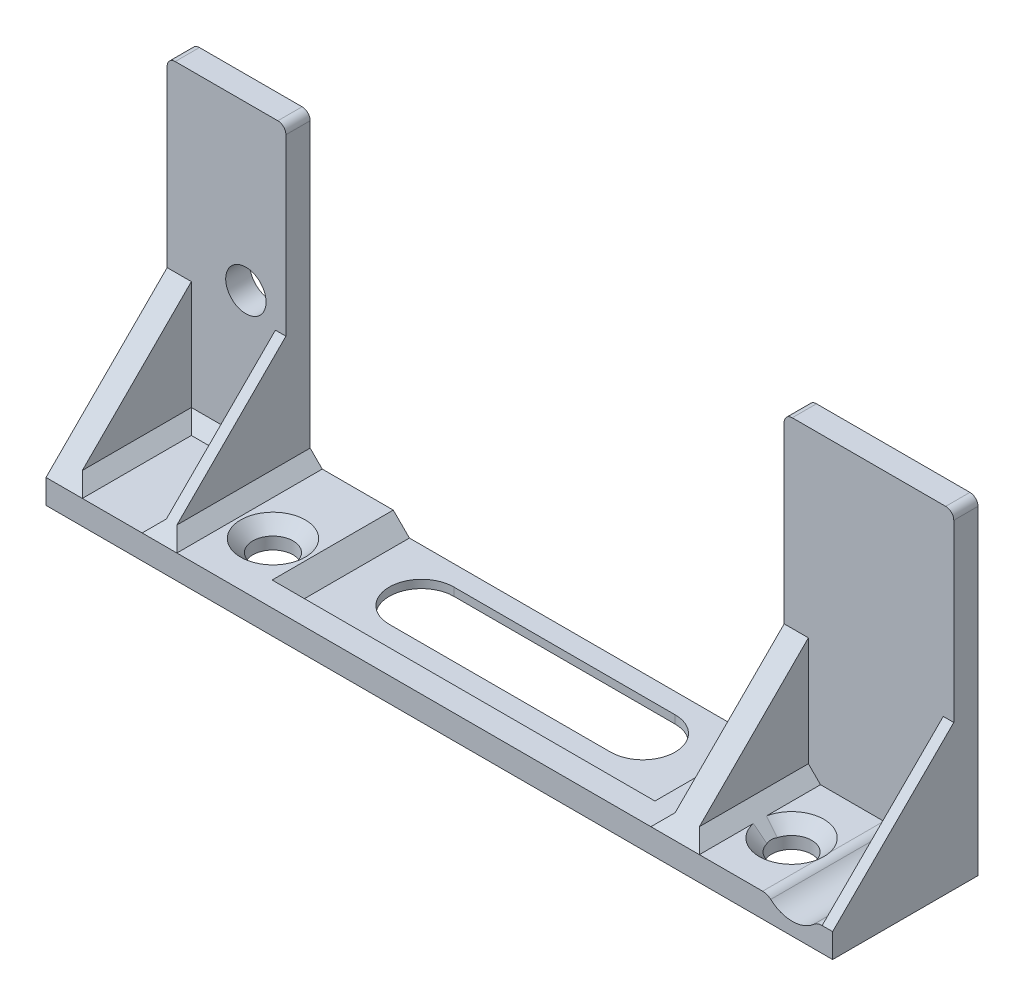
SolidWorks part; units mm, degrees
ref_plane "Plano frontal" through (0, 0, 0) normal (0, 0, 1) x (1, 0, 0)
ref_plane "Plano superior" through (0, 0, 0) normal (0, 1, 0) x (1, 0, 0)
ref_plane "Plano direito" through (0, 0, 0) normal (1, 0, 0) x (0, 0, -1)
sketch "Esboço1" plane through (0, 0, 0) normal (0, 0, 1) x (1, 0, 0)
  line L0 (62.4, 20.175) -> (-33, 20.175)
  line L1 (-34, 19.175) -> (-34, -20.425)
  line L2 (-34, -20.425) -> (63.4, -20.425)
  line L3 (63.4, -20.425) -> (63.4, 19.175)
  line L4 (17.9243, -6.9539) -> (16.3222, -6.7818)
  line L5 (17.9243, -6.9539) -> (18.9922, 2.9889)
  line L6 (18.9922, 2.9889) -> (17.3901, 3.161)
  line L7 (18.2952, -14.6385) -> (17.6127, -1.4836)
  line L8 (9.8273, -18.425) -> (14.7, -18.425)
  line L9 (7.4699, -16.019) -> (9.8273, -18.425)
  line L10 (1.1798, 17.6356) -> (-14.434, 18.7656)
  line L11 (-18.2939, 10.276) -> (-15.8632, 7.7952)
  line L12 (-18.2939, 15.175) -> (-18.2939, 10.276)
  line L13 (51.4, -14.825) -> (51.4, -6.825)
  line L14 (45.4, -14.825) -> (51.4, -14.825)
  line L15 (45.4, -6.825) -> (45.4, -14.825)
  line L16 (51.4, -6.825) -> (45.4, -6.825)
  line L17 (51.4, 7.175) -> (51.4, 15.175)
  line L18 (51.4, 15.175) -> (45.4, 15.175)
  line L19 (45.4, 15.175) -> (45.4, 7.175)
  line L20 (45.4, 7.175) -> (51.4, 7.175)
  line L21 (-29, -13.825) -> (-25, -13.825)
  line L22 (-25, -13.825) -> (-25, -7.825)
  line L23 (-29, -7.825) -> (-29, -13.825)
  line L24 (-25, -7.825) -> (-29, -7.825)
  line L25 (-25, 8.175) -> (-25, 14.175)
  line L26 (-25, 14.175) -> (-29, 14.175)
  line L27 (-29, 14.175) -> (-29, 8.175)
  line L28 (-29, 8.175) -> (-25, 8.175)
  line L29 (23.216, -4.505) -> (23.6432, -0.5279)
  line L30 (23.6432, -0.5279) -> (18.6718, 0.0061)
  line L31 (23.216, -4.505) -> (18.2446, -3.9711)
  arc A0 (-33, 20.175) -> (-34, 19.175) centre (-33, 19.175) ccw
  arc A1 (63.4, 19.175) -> (62.4, 20.175) centre (62.4, 19.175) ccw
  arc A2 (14.7, -18.425) -> (18.2952, -14.6385) centre (14.7, -14.825) ccw
  circle A3 centre (14.7, -14.825) radius 1.75
  circle A4 centre (0, 0) radius 17.675
  arc A5 (-14.434, 18.7656) -> (-18.2939, 15.175) centre (-14.6939, 15.175) ccw
  circle A6 centre (-14.6939, 15.175) radius 1.75
  circle A7 centre (0, 0) radius 1
  circle A8 centre (58.4, -14.825) radius 2
  circle A9 centre (-24.25, 0) radius 2.5
sketch "Esboço2" plane through (0, 0, 0) normal (0, 0, 1) x (1, 0, 0)
  line L8 (-19.2939, 20.175) -> (-19.2939, -17.425)
  line L9 (-18.2939, 15.175) -> (-18.2939, 10.276) construction
  line L10 (42.4, 20.175) -> (42.4, -17.425)
  line L11 (45.4, 15.175) -> (45.4, 7.175) construction
  line L20 (-19.2939, 20.175) -> (-33, 20.175)
  line L21 (42.4, -20.425) -> (63.4, -20.425)
  line L22 (9.8273, -18.425) -> (14.7, -18.425) construction
  line L23 (42.4, -20.425) -> (-19.2939, -20.425)
  line L33 (38.4, -19.425) -> (-9, -19.425)
  line L35 (-19.2939, -17.425) -> (-9, -17.425)
  line L40 (63.4, -20.425) -> (63.4, 19.175) construction
  line L41 (-34, -20.425) -> (63.4, -20.425) construction
  line L42 (-34, 19.175) -> (-34, -20.425) construction
  line L43 (62.4, 20.175) -> (-33, 20.175) construction
  line L44 (-9, -17.425) -> (-9, -19.425)
  line L45 (42.4, -17.425) -> (38.4, -17.425)
  line L46 (38.4, -17.425) -> (38.4, -19.425)
  line L52 (63.4, -20.425) -> (63.4, 19.175)
  line L53 (-34, -20.425) -> (-19.2939, -20.425)
  line L54 (-34, 19.175) -> (-34, -20.425)
  line L55 (62.4, 20.175) -> (42.4, 20.175)
  arc A0 (63.4, 19.175) -> (62.4, 20.175) centre (62.4, 19.175) ccw construction
  arc A1 (-33, 20.175) -> (-34, 19.175) centre (-33, 19.175) ccw construction
  arc A2 (63.4, 19.175) -> (62.4, 20.175) centre (62.4, 19.175) ccw
  arc A3 (-33, 20.175) -> (-34, 19.175) centre (-33, 19.175) ccw
  circle A4 centre (-24.25, 0) radius 2.5 construction
  circle A5 centre (-24.25, 0) radius 2.5
  circle A6 centre (58.4, -14.825) radius 2 construction
  circle A7 centre (58.4, -14.825) radius 2
  dimension "D1" = 1
  dimension "D2" = 3
  dimension "D3" = 1
  dimension "D4" = 25
  dimension "D5" = 25
  dimension "D6" = 3
  dimension "D7" = 3
extrude "Ressalto-extrusão1" add sketch "Esboço2" along normal blind 3
sketch "Esboço3" plane through (0, 0, 0) normal (0, 0, -1) x (-1, 0, 0)
  line L24 (-51.1, 14.875) -> (-51.1, 7.475)
  line L25 (-45.7, 14.875) -> (-51.1, 14.875)
  line L26 (-45.7, 7.475) -> (-45.7, 14.875)
  line L27 (-51.1, 7.475) -> (-45.7, 7.475)
  line L28 (-51.1, 14.875) -> (-51.1, 7.475)
  line L29 (-45.7, 14.875) -> (-51.1, 14.875)
  line L30 (-45.7, 7.475) -> (-45.7, 14.875)
  line L31 (-51.1, 7.475) -> (-45.7, 7.475)
  line L36 (-51.1, -7.125) -> (-51.1, -14.525)
  line L37 (-45.7, -7.125) -> (-51.1, -7.125)
  line L38 (-45.7, -14.525) -> (-45.7, -7.125)
  line L39 (-51.1, -14.525) -> (-45.7, -14.525)
  line L40 (-51.1, -7.125) -> (-51.1, -14.525)
  line L41 (-45.7, -7.125) -> (-51.1, -7.125)
  line L42 (-45.7, -14.525) -> (-45.7, -7.125)
  line L43 (-51.1, -14.525) -> (-45.7, -14.525)
  line L48 (25.3, 13.875) -> (25.3, 8.475)
  line L49 (28.7, 13.875) -> (25.3, 13.875)
  line L50 (28.7, 8.475) -> (28.7, 13.875)
  line L51 (25.3, 8.475) -> (28.7, 8.475)
  line L52 (25.3, 13.875) -> (25.3, 8.475)
  line L53 (28.7, 13.875) -> (25.3, 13.875)
  line L54 (28.7, 8.475) -> (28.7, 13.875)
  line L55 (25.3, 8.475) -> (28.7, 8.475)
  line L60 (28.7, -13.525) -> (28.7, -8.125)
  line L61 (25.3, -13.525) -> (28.7, -13.525)
  line L62 (25.3, -8.125) -> (25.3, -13.525)
  line L63 (28.7, -8.125) -> (25.3, -8.125)
  line L64 (28.7, -13.525) -> (28.7, -8.125)
  line L65 (25.3, -13.525) -> (28.7, -13.525)
  line L66 (25.3, -8.125) -> (25.3, -13.525)
  line L67 (28.7, -8.125) -> (25.3, -8.125)
  dimension "D1" = 0.3
  dimension "D2" = 0.3
  dimension "D3" = 0.3
  dimension "D4" = 0.3
extrude "Ressalto-extrusão2" add sketch "Esboço3" along normal blind 1.2
sketch "Esboço4" plane through (0, 0, 3) normal (0, 0, 1) x (1, 0, 0)
  line L9 (63.4, -20.425) -> (63.4, 19.175) construction
  line L10 (-34, -20.425) -> (63.4, -20.425)
  line L11 (-34, -20.425) -> (-34, -17.425)
  line L12 (-34, -17.425) -> (-9, -17.425)
  line L13 (63.4, -20.425) -> (63.4, -17.425)
  line L14 (38.4, -17.425) -> (38.4, -19.425)
  line L15 (38.4, -19.425) -> (-9, -19.425)
  line L16 (-9, -19.425) -> (-9, -17.425)
  line L17 (38.4, -17.425) -> (55.3603, -17.425)
  line L18 (61.4397, -17.425) -> (63.4, -17.425)
  arc A0 (55.3603, -17.425) -> (61.4397, -17.425) centre (58.4, -14.825) ccw
  dimension "D2" = 8
  dimension "D1" = 3
extrude "Ressalto-extrusão3" add sketch "Esboço4" along normal blind 15
chamfer "Chanfro1" distance 2 angle 45 2 edges at (38.4, -19.425, 9) (-9, -19.425, 9)
fillet "Filete1" radius 1.5 2 edges at (61.4397, -17.425, 10.5) (55.3603, -17.425, 10.5)
fillet "Filete2" radius 1 2 edges at (42.4, 20.175, 1.5) (-19.2939, 20.175, 1.5)
sketch "Esboço6" plane through (-34, 0, 0) normal (-1, 0, 0) x (0, 0, 1)
  line L0 (18, -17.425) -> (3, -2.425)
  line L1 (18, -17.425) -> (3, -17.425) construction
  line L2 (18, -17.425) -> (3, -17.425)
  line L3 (3, -17.425) -> (3, -2.425)
  dimension "D1" = 45
extrude "Ressalto-extrusão4" add sketch "Esboço6" against normal blind 3
sketch "Esboço7" plane through (63.4, 0, 0) normal (1, 0, 0) x (0, 0, -1)
  line L0 (-18, -17.425) -> (-3, -2.5)
  line L1 (-3, -2.5) -> (-3, -17.425)
  line L2 (-3, -17.425) -> (-18, -17.425)
extrude "Ressalto-extrusão5" add sketch "Esboço7" against normal blind 1.3
sketch "Esboço8" plane through (-19.2939, 0, 0) normal (1, 0, 0) x (0, 0, -1)
  line L1 (-3, 19.175) -> (-3, -2.425) construction
  line L2 (-18, -17.425) -> (-3, -2.425) construction
  line L4 (-3, -2.425) -> (-3, -17.425)
  line L5 (-18, -17.425) -> (-3, -2.425)
  line L6 (-18, -17.425) -> (-3, -17.425)
extrude "Ressalto-extrusão6" add sketch "Esboço8" against normal blind 1.3
sketch "Esboço9" plane through (42.4, 0, 0) normal (-1, 0, 0) x (0, 0, 1)
  line L1 (3, 19.175) -> (3, -2.425) construction
  line L2 (18, -17.425) -> (3, -2.425) construction
  line L4 (3, -2.425) -> (3, -17.425)
  line L5 (18, -17.425) -> (3, -2.425)
  line L6 (18, -17.425) -> (3, -17.425)
extrude "Ressalto-extrusão7" add sketch "Esboço9" against normal blind 3
chamfer "Chanfro2" distance 1.5 angle 45 6 edges at (45.4, -17.425, 10.5) (42.4, -17.425, 9) (-20.5939, -17.425, 10.5) (-31, -17.425, 10.5) (-25.7969, -17.425, 3) (-19.2939, -17.425, 9) tangent propagation no
sketch "Esboço10" plane through (0, -17.425, 0) normal (0, 1, 0) x (1, 0, 0)
  line L0 (-34, -10.5) -> (63.4, -10.5) construction
  line L1 (-34, -18) -> (-34, -3) construction
  line L2 (63.4, -3) -> (63.4, -18) construction
  line L3 (-13.3969, -18) -> (-13.3969, -10.5) construction
  line L4 (-9, -18) -> (-17.7939, -18) construction
  line L5 (50.817, -18) -> (50.817, -10.5) construction
  line L6 (54.7339, -18) -> (46.9, -18) construction
  circle A0 centre (-13.3969, -10.5) radius 2.5
  circle A1 centre (50.817, -10.5) radius 2.5
  dimension "D1" = 5
  dimension "D2" = 5
extrude "Corte-extrusão1" cut sketch "Esboço10" against normal blind 13
chamfer "Chanfro3" distance 1.5 angle 45 2 edges at (50.817, -17.425, 13) (-13.3969, -17.425, 13)
sketch "Esboço11" plane through (0, -19.425, 0) normal (0, 1, 0) x (1, 0, 0)
  line L0 (36.4, 0) -> (-7, 0) construction
  line L1 (-7, 0) -> (-7, -18) construction
  line L2 (36.4, -18) -> (36.4, 0) construction
  line L3 (1, -6.5) -> (28.4, -6.5) construction
  line L4 (1, -2.5) -> (28.4, -2.5)
  line L5 (1, -10.5) -> (28.4, -10.5)
  arc A0 (1, -2.5) -> (1, -10.5) centre (1, -6.5) ccw
  arc A1 (28.4, -10.5) -> (28.4, -2.5) centre (28.4, -6.5) ccw
  point P8 (14.7, -6.5)
  dimension "D1" = 8
  dimension "D2" = 8
  dimension "D3" = 8
  dimension "D4" = 6.5
extrude "Corte-extrusão2" cut sketch "Esboço11" against normal blind 13
sketch "Esboço12" plane through (0, 0, 18) normal (0, 0, 1) x (1, 0, 0)
  line L0 (-34, -20.425) -> (63.4, -20.425) construction
  line L1 (-9, -17.425) -> (38.4, -17.425)
  line L2 (-9, -17.425) -> (-9, -20.425)
  line L3 (-9, -20.425) -> (38.4, -20.425)
  line L4 (38.4, -17.425) -> (38.4, -20.425)
extrude "Ressalto-extrusão8" add sketch "Esboço12" against normal blind 3
chamfer "Chanfro4" distance 2 angle 45 1 edges at (14.7, -19.425, 15)
